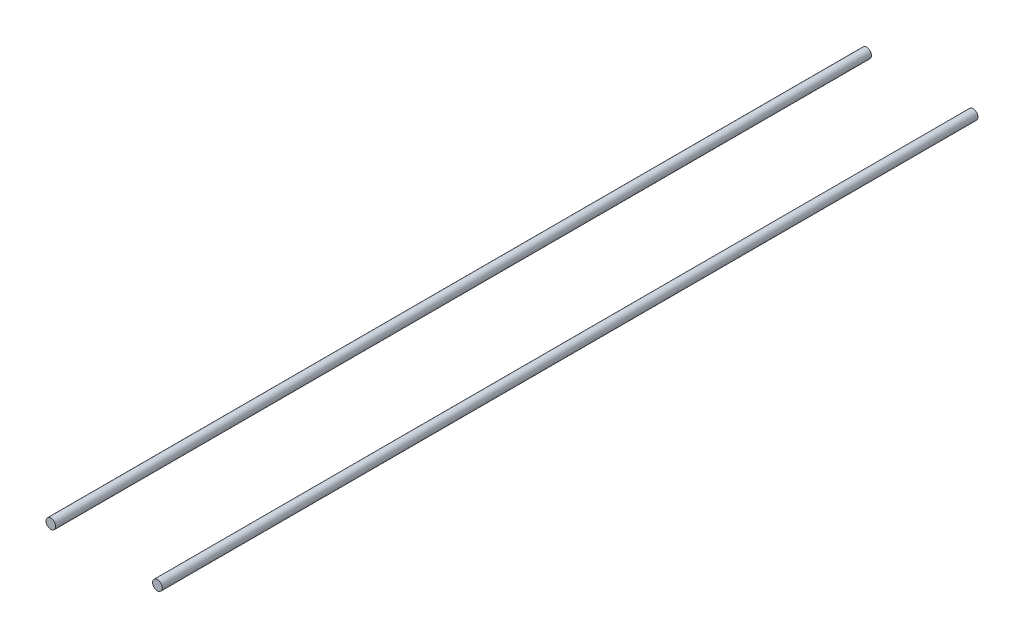
SolidWorks part; units mm, degrees
ref_plane "Front Plane" through (0, 0, 0) normal (0, 0, 1) x (1, 0, 0)
ref_plane "Top Plane" through (0, 0, 0) normal (0, 1, 0) x (1, 0, 0)
ref_plane "Right Plane" through (0, 0, 0) normal (1, 0, 0) x (0, 0, -1)
ref_plane "Plane1" through (0, 0, 200) normal (0, 0, -1) x (-1, 0, 0)
sketch "Sketch1" plane through (0, 0, 200) normal (0, 0, -1) x (-1, 0, 0)
  line L0 (-90.0001, -30.8878) -> (89.9999, -30.8878) construction
  line L1 (0, 70.1122) -> (0, -75.0001) construction
  line L2 (-50.5, -30.8878) -> (50.5, -30.8878) construction
  line L3 (-50.5, -30.8878) -> (-50.5, 70.1122) construction
  line L4 (-50.5, 70.1122) -> (50.5, 70.1122) construction
  line L5 (50.5, -30.8878) -> (50.5, 70.1122) construction
  circle A0 centre (-65.5, -30.8878) radius 6
  circle A2 centre (65.5, -30.8878) radius 6
  spline S0 degree 3 poles (-95, 100.1689) (-95, 99.9993) (-95, 99.9964) (-95, 99.9928) (-95, 99.9874) (-95, 99.9749) (-95, 99.9497) (-95, 99.8995) (-95, 99.799) (-95, 99.598) (-95, 99.196) (-95, 98.392) (-95, 96.784) (-95, 93.5679) (-95, 87.1359) (-95, 81.6227) (-95, 70.5964) (-95, 63.2455) (-95, 41.1927) (-95, 22.8155) (-95, 4.2085) (-95, 0.3033) (-95, -0.0413) (-95, -0.15) (-94.9995, -0.3707) (-94.9976, -0.9224) (-94.9829, -2.3558) (-94.9471, -3.6763) (-94.8447, -6.313) (-94.7351, -8.0652) (-94.2711, -13.2968) (-93.781, -16.7505) (-92.3743, -23.5302) (-91.4572, -26.8546) (-89.7203, -31.6821) (-89.0817, -33.2636) (-87.6794, -36.3621) (-86.9158, -37.8795) (-85.2643, -40.8354) (-84.3762, -42.2733) (-82.4744, -45.0646) (-81.4616, -46.4169) (-78.2486, -50.3244) (-75.8666, -52.7366) (-70.7044, -57.1297) (-67.9222, -59.1147) (-62.0605, -62.6615) (-58.9802, -64.2249) (-52.6088, -66.9709) (-49.3209, -68.1542) (-42.6122, -70.189) (-39.1884, -71.041) (-32.2538, -72.4676) (-28.7476, -73.0417) (-21.6814, -73.9534) (-18.1202, -74.2916) (-10.9713, -74.772) (-7.3829, -74.9132) (-1.9872, -74.9989) (-0.1854, -75.0066) (3.415, -74.9827) (5.2133, -74.9505) (10.6005, -74.7874) (14.1817, -74.5902) (21.3129, -73.9887) (24.8595, -73.5849) (31.8912, -72.5281) (35.3791, -71.8753) (42.2571, -70.2781) (45.6447, -69.3328) (52.266, -67.0957) (55.5033, -65.8035) (61.7404, -62.827) (64.7415, -61.1407) (68.9962, -58.292) (70.3742, -57.2887) (73.0346, -55.1767) (74.316, -54.0684) (76.7745, -51.745) (77.9514, -50.5304) (80.1884, -48.0037) (81.2482, -46.691) (84.2485, -42.6117) (86.0017, -39.7107) (89.0071, -33.6212) (90.2575, -30.4376) (92.2908, -23.8805) (93.0733, -20.5094) (94.2309, -13.6581) (94.6061, -10.1784) (94.9124, -4.9201) (94.9865, -2.7208) (94.9997, -0.5145) (95, 0.0374) (95, 0.1537) (95, 0.3835) (95, 0.728) (95, 1.9915) (95, 17.8419) (95, 33.4625) (95, 62.8662) (95, 79.4057) (95, 96.4047) (95, 98.9315) (95, 99.6494) (95, 99.9222) (95, 99.9689) (95, 99.9868) (95, 99.994) (95, 99.9991) (95, 100.003) (95, 100.0268) (94.9991, 100.0925) (94.9961, 100.1546) (94.9877, 100.2775) (94.9785, 100.3573) (94.954, 100.5109) (94.9391, 100.5827) (94.8816, 100.8069) (94.8258, 100.9667) (94.6797, 101.2883) (94.5845, 101.4611) (94.3455, 101.8226) (94.2016, 102.0114) (93.8582, 102.4054) (93.6595, 102.6093) (93.2238, 103.0127) (92.9849, 103.2141) (92.4673, 103.6145) (92.1876, 103.8143) (91.5989, 104.2064) (91.292, 104.3973) (90.3356, 104.9562) (89.6468, 105.3123) (88.2144, 105.9838) (87.4677, 106.3002) (85.9329, 106.8992) (85.1471, 107.1807) (82.7417, 107.9818) (81.0852, 108.4554) (77.7141, 109.3132) (75.9985, 109.6974) (72.534, 110.3975) (70.7842, 110.7134) (65.502, 111.5804) (61.9373, 112.0522) (54.7681, 112.8552) (51.1631, 113.1855) (43.9313, 113.7435) (40.3036, 113.9709) (33.036, 114.3479) (29.3958, 114.4967) (18.4613, 114.8506) (11.1566, 114.9634) (0.1894, 115.007) (-3.4683, 115.0012) (-10.7775, 114.9459) (-14.4303, 114.8958) (-25.379, 114.6647) (-32.667, 114.4055) (-43.5566, 113.7666) (-47.1781, 113.5116) (-54.395, 112.8882) (-57.9912, 112.5207) (-65.1309, 111.6267) (-68.677, 111.1011) (-73.9138, 110.1299) (-75.6447, 109.7754) (-79.0596, 108.9861) (-80.7447, 108.5514) (-84.0288, 107.5758) (-85.6293, 107.0349) (-87.9085, 106.1152) (-88.6431, 105.7923) (-89.7002, 105.2767) (-90.0453, 105.0996) (-90.7111, 104.7379) (-91.0327, 104.5527) (-91.6515, 104.1727) (-91.9503, 103.9768) (-92.5142, 103.5798) (-92.7778, 103.3797) (-93.2639, 102.9777) (-93.4864, 102.7759) (-93.8894, 102.3722) (-94.0685, 102.1714) (-94.37, 101.7895) (-94.4935, 101.6073) (-94.6953, 101.2591) (-94.7711, 101.0982) (-94.8605, 100.8603) (-94.8858, 100.7823) (-94.9279, 100.6307) (-94.9442, 100.5592) (-94.985, 100.3327) (-95, 100.1689) (-95, 99.9993) (-95, 99.9964) knots -0.001953 -0.001953 0 0 0.000008 0.000008 0.000015 0.000031 0.000061 0.000122 0.000244 0.000488 0.000977 0.001953 0.003906 0.007812 0.015625 0.03125 0.03125 0.0625 0.0625 0.125 0.140625 0.141602 0.141602 0.14209 0.14209 0.142578 0.144531 0.148437 0.148437 0.15625 0.15625 0.171875 0.171875 0.1875 0.1875 0.195312 0.195312 0.203125 0.203125 0.210937 0.210937 0.21875 0.21875 0.234375 0.234375 0.25 0.25 0.265625 0.265625 0.28125 0.28125 0.296875 0.296875 0.3125 0.3125 0.328125 0.328125 0.34375 0.34375 0.351562 0.351562 0.359375 0.359375 0.375 0.375 0.390625 0.390625 0.40625 0.40625 0.421875 0.421875 0.4375 0.4375 0.453125 0.453125 0.460937 0.460937 0.46875 0.46875 0.476562 0.476562 0.484375 0.484375 0.5 0.5 0.515625 0.515625 0.53125 0.53125 0.546875 0.546875 0.554687 0.556641 0.556641 0.557129 0.557129 0.557617 0.558594 0.5625 0.625 0.625 0.6875 0.695312 0.697266 0.698242 0.698364 0.698425 0.698441 0.698441 0.698456 0.698456 0.698486 0.69873 0.699219 0.699219 0.700195 0.700195 0.701172 0.701172 0.703125 0.703125 0.705078 0.705078 0.707031 0.707031 0.708984 0.708984 0.710937 0.710937 0.712891 0.712891 0.714844 0.714844 0.71875 0.71875 0.722656 0.722656 0.726562 0.726562 0.734375 0.734375 0.742187 0.742187 0.75 0.75 0.765625 0.765625 0.78125 0.78125 0.796875 0.796875 0.8125 0.8125 0.84375 0.84375 0.859375 0.859375 0.875 0.875 0.90625 0.90625 0.921875 0.921875 0.9375 0.9375 0.953125 0.953125 0.960937 0.960937 0.96875 0.96875 0.976562 0.976562 0.980469 0.980469 0.982422 0.982422 0.984375 0.984375 0.986328 0.986328 0.988281 0.988281 0.990234 0.990234 0.992187 0.992187 0.994141 0.994141 0.996094 0.996094 0.99707 0.99707 0.998047 0.998047 1 1 1.000008 1.000008 1.000015 only from (-95, 100) to (-95, 100) construction
  point P7 (0, 70.1122)
  dimension "D4" = 12
  dimension "D1" = 180
  dimension "D2" = 101
  dimension "D3" = 101
  dimension "D5" = 15
extrude "Boss-Extrude2" add sketch "Sketch1" along normal blind 100 and the other way blind 903.2
